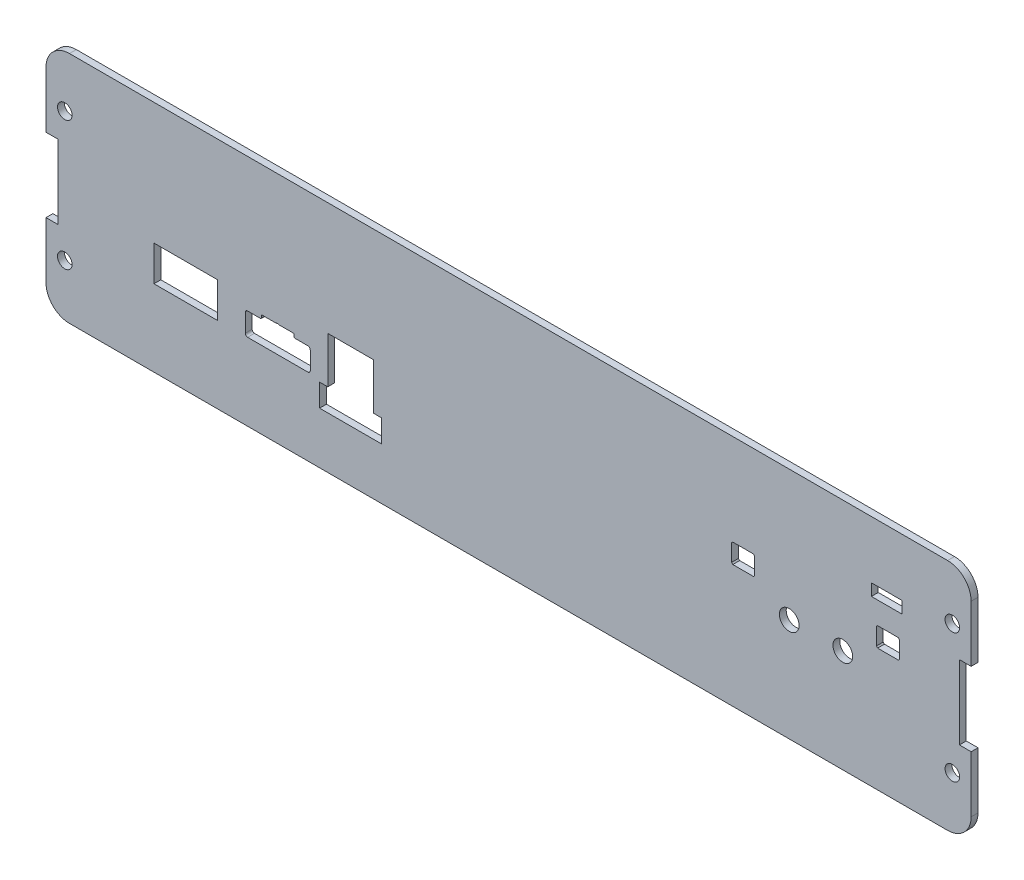
SolidWorks part; units mm, degrees
ref_plane "Front Plane" through (0, 0, 0) normal (0, 0, 1) x (1, 0, 0)
ref_plane "Top Plane" through (0, 0, 0) normal (0, 1, 0) x (1, 0, 0)
ref_plane "Right Plane" through (0, 0, 0) normal (1, 0, 0) x (0, 0, -1)
sketch "Sketch2" plane through (0, 0, 0) normal (0, 0, 1) x (1, 0, 0)
  line L0 (118.618, 31.5722) -> (-118.618, 31.5722)
  line L1 (-124.968, 25.2222) -> (-124.968, 9.9822)
  line L2 (-124.968, 9.9822) -> (-121.793, 9.9822)
  line L3 (-121.793, 9.9822) -> (-121.793, -9.9822)
  line L4 (0, 0) -> (0, 31.5722) construction
  line L5 (0, 0) -> (-121.793, 0) construction
  line L6 (124.968, 25.2222) -> (124.968, 9.9822)
  line L7 (124.968, 9.9822) -> (121.793, 9.9822)
  line L8 (121.793, 9.9822) -> (121.793, -9.9822)
  line L9 (124.968, -9.9822) -> (121.793, -9.9822)
  line L10 (124.968, -25.2222) -> (124.968, -9.9822)
  line L11 (-124.968, -9.9822) -> (-121.793, -9.9822)
  line L12 (-124.968, -25.2222) -> (-124.968, -9.9822)
  line L13 (118.618, -31.5722) -> (-118.618, -31.5722)
  arc A0 (-124.968, 25.2222) -> (-118.618, 31.5722) centre (-118.618, 25.2222) cw
  arc A1 (124.968, 25.2222) -> (118.618, 31.5722) centre (118.618, 25.2222) ccw
  arc A2 (124.968, -25.2222) -> (118.618, -31.5722) centre (118.618, -25.2222) cw
  arc A3 (-124.968, -25.2222) -> (-118.618, -31.5722) centre (-118.618, -25.2222) ccw
  point P22 (121.793, 0)
  point P25 (-124.968, -17.6022)
  dimension "D1" = 6.35
  dimension "D2" = 3.175
  dimension "D3" = 21.59
  dimension "D4" = 9.9822
  dimension "D5" = 249.936
extrude "MainBody" add sketch "Sketch2" along normal blind 1.8542
sketch "Sketch3" plane through (0, 0, 1.8542) normal (0, 0, 1) x (1, 0, 0)
  line L0 (118.618, 31.5722) -> (-118.618, 31.5722) construction
  line L2 (0, 31.5722) -> (0, 0) construction
  line L3 (0, 0) -> (-121.793, 0) construction
  line L4 (-121.793, 9.9822) -> (-121.793, -9.9822) construction
  circle A0 centre (-119.888, 17.4625) radius 1.9685
  circle A1 centre (119.888, 17.4625) radius 1.9685
  circle A2 centre (119.888, -17.4625) radius 1.9685
  circle A3 centre (-119.888, -17.4625) radius 1.9685
  dimension "D1" = 3.937
  dimension "D2" = 17.4625
  dimension "D3" = 119.888
extrude "MountHoles" cut sketch "Sketch3" against normal through all
ref_axis "MntTopLeft" through (-119.888, 17.4625, 0) along (0, 0, 1)
ref_axis "MntBottomLeft" through (-119.888, -17.4625, 0) along (0, 0, 1)
ref_axis "MntTopRight" through (119.888, 17.4625, 0) along (0, 0, 1)
ref_axis "MntBottomRight" through (119.888, -17.4625, 0) along (0, 0, 1)
ref_plane "ExtFront" through (0, 0, 1.8542) normal (0, 0, 1) x (1, 0, 0)
ref_plane "IntFront" through (0, 0, 0) normal (0, 0, -1) x (-1, 0, 0)
ref_plane "TBCenter" through (0, 0, 0) normal (0, 1, 0) x (1, 0, 0)
ref_plane "LRCenter" through (0, 0, 0) normal (-1, 0, 0) x (0, 0, 1)
sketch "Sketch4" plane through (0, 0, 1.8542) normal (0, 0, 1) x (1, 0, 0)
  line L17 (98.0188, 16.0672) -> (98.0188, 12.8739)
  line L18 (98.0188, 12.8739) -> (106.2988, 12.8739)
  line L19 (106.2988, 12.8739) -> (106.2988, 16.0672)
  line L20 (106.2988, 16.0672) -> (98.0188, 16.0672)
  line L21 (98.0188, 16.0672) -> (98.0188, 12.8739)
  line L22 (98.0188, 12.8739) -> (106.2988, 12.8739)
  line L23 (106.2988, 12.8739) -> (106.2988, 16.0672)
  line L24 (106.2988, 16.0672) -> (98.0188, 16.0672)
  line L51 (-78.6869, -10.8814) -> (-78.6869, -1.3564)
  line L52 (-87.2457, -10.8814) -> (-78.6869, -10.8814)
  line L53 (-95.8066, -10.8814) -> (-87.2457, -10.8814)
  line L54 (-95.8066, -1.3564) -> (-95.8066, -10.8814)
  line L55 (-87.2457, -1.3564) -> (-95.8066, -1.3564)
  line L56 (-78.6869, -1.3564) -> (-87.2457, -1.3564)
  line L57 (-78.6869, -10.8814) -> (-78.6869, -1.3564)
  line L58 (-87.2457, -10.8814) -> (-78.6869, -10.8814)
  line L59 (-95.8066, -10.8814) -> (-87.2457, -10.8814)
  line L60 (-95.8066, -1.3564) -> (-95.8066, -10.8814)
  line L61 (-87.2457, -1.3564) -> (-95.8066, -1.3564)
  line L62 (-78.6869, -1.3564) -> (-87.2457, -1.3564)
  line L229 (-71.1318, -5.2274) -> (-71.1318, -10.1274)
  line L230 (-70.5048, -10.7544) -> (-54.2048, -10.7544)
  line L231 (-53.5778, -10.1274) -> (-53.5778, -5.2274)
  line L232 (-54.2048, -4.6004) -> (-57.6548, -4.6004)
  line L233 (-58.0278, -4.2274) -> (-58.0278, -3.6004)
  line L234 (-58.0278, -3.6004) -> (-62.0278, -3.6004)
  line L235 (-62.0278, -3.6004) -> (-62.0278, -3.5004)
  line L236 (-62.0278, -3.5004) -> (-62.3548, -3.5004)
  line L237 (-62.6818, -3.5004) -> (-62.6818, -3.6004)
  line L238 (-62.3548, -3.5004) -> (-62.6818, -3.5004)
  line L239 (-62.6818, -3.6004) -> (-66.6818, -3.6004)
  line L240 (-66.6818, -3.6004) -> (-66.6818, -4.2274)
  line L241 (-67.0548, -4.6004) -> (-70.5048, -4.6004)
  line L242 (-71.1318, -5.2274) -> (-71.1318, -10.1274)
  line L243 (-70.5048, -10.7544) -> (-54.2048, -10.7544)
  line L244 (-53.5778, -10.1274) -> (-53.5778, -5.2274)
  line L245 (-54.2048, -4.6004) -> (-57.6548, -4.6004)
  line L246 (-58.0278, -4.2274) -> (-58.0278, -3.6004)
  line L247 (-58.0278, -3.6004) -> (-62.0278, -3.6004)
  line L248 (-62.0278, -3.6004) -> (-62.0278, -3.5004)
  line L249 (-62.0278, -3.5004) -> (-62.3548, -3.5004)
  line L250 (-62.6818, -3.5004) -> (-62.6818, -3.6004)
  line L251 (-62.3548, -3.5004) -> (-62.6818, -3.5004)
  line L252 (-62.6818, -3.6004) -> (-66.6818, -3.6004)
  line L253 (-66.6818, -3.6004) -> (-66.6818, -4.2274)
  line L254 (-67.0548, -4.6004) -> (-70.5048, -4.6004)
  line L286 (-36.5518, -11.5164) -> (-36.5518, 0.9996)
  line L287 (-34.2878, -11.5164) -> (-36.5518, -11.5164)
  line L288 (-34.2878, -17.6124) -> (-34.2878, -11.5164)
  line L289 (-51.0518, -17.6124) -> (-34.2878, -17.6124)
  line L290 (-51.0518, -11.5164) -> (-51.0518, -17.6124)
  line L291 (-48.8418, -11.5164) -> (-51.0518, -11.5164)
  line L292 (-48.8418, 0.9996) -> (-48.8418, -11.5164)
  line L293 (-36.5518, 0.9996) -> (-48.8418, 0.9996)
  line L294 (-36.5518, -11.5164) -> (-36.5518, 0.9996)
  line L295 (-34.2878, -11.5164) -> (-36.5518, -11.5164)
  line L296 (-34.2878, -17.6124) -> (-34.2878, -11.5164)
  line L297 (-51.0518, -17.6124) -> (-34.2878, -17.6124)
  line L298 (-51.0518, -11.5164) -> (-51.0518, -17.6124)
  line L299 (-48.8418, -11.5164) -> (-51.0518, -11.5164)
  line L300 (-48.8418, 0.9996) -> (-48.8418, -11.5164)
  line L301 (-36.5518, 0.9996) -> (-48.8418, 0.9996)
  line L346 (60.2488, 6.5473) -> (60.2488, 1.9462)
  line L347 (60.2488, 1.9462) -> (60.5772, 1.6179)
  line L348 (60.5772, 1.6179) -> (66.1688, 1.6179)
  line L349 (66.1688, 1.6179) -> (66.4972, 1.9462)
  line L350 (66.4972, 1.9462) -> (66.4972, 6.5473)
  line L351 (66.4972, 6.5473) -> (66.1688, 6.8757)
  line L352 (66.1688, 6.8757) -> (60.5772, 6.8757)
  line L353 (60.5772, 6.8757) -> (60.2488, 6.5473)
  line L354 (60.2488, 6.5473) -> (60.2488, 1.9462)
  line L355 (60.2488, 1.9462) -> (60.5772, 1.6179)
  line L356 (60.5772, 1.6179) -> (66.1688, 1.6179)
  line L357 (66.1688, 1.6179) -> (66.4972, 1.9462)
  line L358 (66.4972, 1.9462) -> (66.4972, 6.5473)
  line L359 (66.4972, 6.5473) -> (66.1688, 6.8757)
  line L360 (66.1688, 6.8757) -> (60.5772, 6.8757)
  line L361 (60.5772, 6.8757) -> (60.2488, 6.5473)
  line L398 (99.3648, 6.5473) -> (99.3648, 1.9462)
  line L399 (99.3648, 1.9462) -> (99.6932, 1.6179)
  line L400 (99.6932, 1.6179) -> (105.2848, 1.6179)
  line L401 (105.2848, 1.6179) -> (105.6132, 1.9462)
  line L402 (105.6132, 1.9462) -> (105.6132, 6.5473)
  line L403 (105.6132, 6.5473) -> (105.2848, 6.8757)
  line L404 (105.2848, 6.8757) -> (99.6932, 6.8757)
  line L405 (99.6932, 6.8757) -> (99.3648, 6.5473)
  line L406 (99.3648, 6.5473) -> (99.3648, 1.9462)
  line L407 (99.3648, 1.9462) -> (99.6932, 1.6179)
  line L408 (99.6932, 1.6179) -> (105.2848, 1.6179)
  line L409 (105.2848, 1.6179) -> (105.6132, 1.9462)
  line L410 (105.6132, 1.9462) -> (105.6132, 6.5473)
  line L411 (105.6132, 6.5473) -> (105.2848, 6.8757)
  line L412 (105.2848, 6.8757) -> (99.6932, 6.8757)
  line L413 (99.6932, 6.8757) -> (99.3648, 6.5473)
  circle A57 centre (90.297, -3.7295) radius 2.667
  circle A58 centre (90.297, -3.7295) radius 2.667
  circle A60 centre (75.819, -3.7295) radius 2.667
  arc A61 (-70.5048, -4.6004) -> (-71.1318, -5.2274) centre (-70.5048, -5.2274) ccw
  arc A62 (-71.1318, -10.1274) -> (-70.5048, -10.7544) centre (-70.5048, -10.1274) ccw
  arc A63 (-54.2048, -10.7544) -> (-53.5778, -10.1274) centre (-54.2048, -10.1274) ccw
  arc A64 (-53.5778, -5.2274) -> (-54.2048, -4.6004) centre (-54.2048, -5.2274) ccw
  arc A65 (-58.0278, -4.2274) -> (-57.6548, -4.6004) centre (-57.6548, -4.2274) ccw
  arc A66 (-67.0548, -4.6004) -> (-66.6818, -4.2274) centre (-67.0548, -4.2274) ccw
  arc A67 (-70.5048, -4.6004) -> (-71.1318, -5.2274) centre (-70.5048, -5.2274) ccw
  arc A68 (-71.1318, -10.1274) -> (-70.5048, -10.7544) centre (-70.5048, -10.1274) ccw
  arc A69 (-54.2048, -10.7544) -> (-53.5778, -10.1274) centre (-54.2048, -10.1274) ccw
  arc A70 (-53.5778, -5.2274) -> (-54.2048, -4.6004) centre (-54.2048, -5.2274) ccw
  arc A71 (-58.0278, -4.2274) -> (-57.6548, -4.6004) centre (-57.6548, -4.2274) ccw
  arc A72 (-67.0548, -4.6004) -> (-66.6818, -4.2274) centre (-67.0548, -4.2274) ccw
  circle A73 centre (75.819, -3.7295) radius 2.667
  dimension "D1" = 0.127
  dimension "D2" = 0.127
  dimension "D3" = 0.127
  dimension "D4" = 0.127
  dimension "D5" = 0.127
  dimension "D6" = 0.127
  dimension "D7" = 0.127
  dimension "D8" = 0.127
extrude "PanelCutout" cut sketch "Sketch4" against normal up to next
equation "\"MainBodyExtWidth\"=9.84"
equation "\"MainBodyExtHeight\"=2.52"
equation "\"D4@Sketch2\"=0.786/2in"
equation "\"D5@Sketch2\"=\"MainBodyExtWidth\""
equation "\"MainBodyThickness\"= 0.073"
equation "\"D1@MainBody\" = \"MainBodyThickness\""
equation "\"ScrewMountSize\"=0.155"
equation "\"D1@Sketch3\"=\"ScrewMountSize\""
